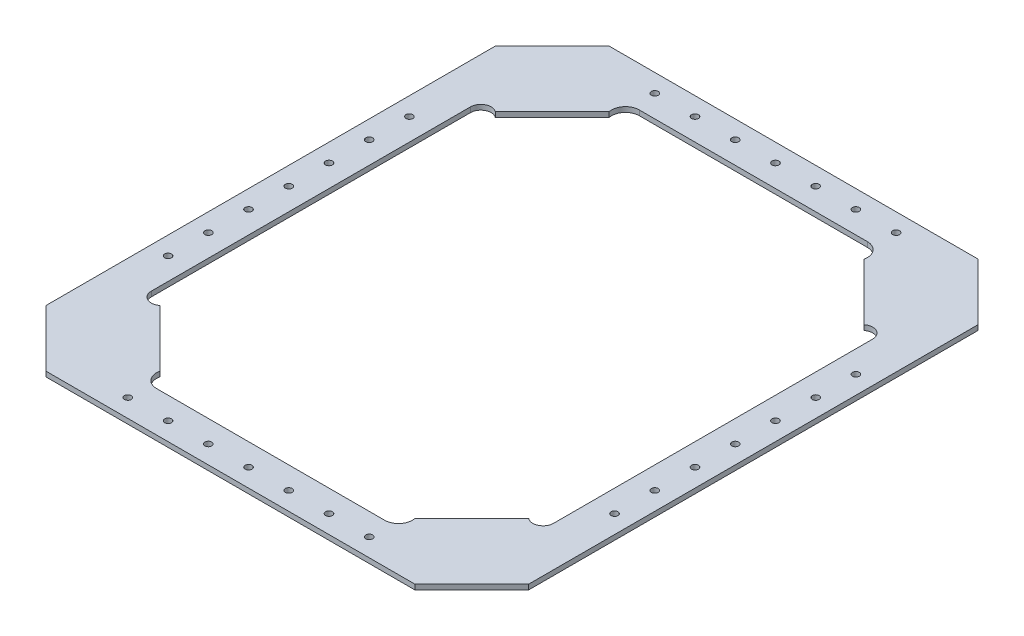
SolidWorks part; units mm, degrees
ref_plane "Front Plane" through (0, 0, 0) normal (0, 0, 1) x (1, 0, 0)
ref_plane "Top Plane" through (0, 0, 0) normal (0, 1, 0) x (1, 0, 0)
ref_plane "Right Plane" through (0, 0, 0) normal (1, 0, 0) x (0, 0, -1)
sketch "Sketch1" plane through (0, 0, 0) normal (0, 1, 0) x (1, 0, 0)
  line L0 (-152.4, 119.0596) -> (-116.479, 154.9807)
  line L1 (-116.479, 154.9807) -> (116.479, 154.9807)
  line L2 (-152.4, 119.0596) -> (-152.4, -164.6983)
  line L3 (152.4, 119.0596) -> (152.4, -164.6983)
  line L4 (152.4, 119.0596) -> (116.479, 154.9807)
  line L5 (0, 154.9807) -> (0, -200.6193) construction
  line L6 (-152.4, -22.8193) -> (152.4, -22.8193) construction
  line L7 (152.4, -164.6983) -> (116.479, -200.6193)
  line L8 (-116.479, -200.6193) -> (116.479, -200.6193)
  line L9 (-152.4, -164.6983) -> (-116.479, -200.6193)
  point P9 (0, -22.8193)
  point P11 (0, -22.8193)
  dimension "D1" = 355.6
  dimension "D3" = 50.8
  dimension "D4" = 135
extrude "Boss-Extrude1" add sketch "Sketch1" along normal blind 3.175
sketch "Sketch2" plane through (0, 3.175, 0) normal (0, 1, 0) x (1, 0, 0)
  line L0 (-152.4, -22.8193) -> (199.0625, -22.8193) construction
  line L1 (-152.4, 119.0596) -> (-152.4, -164.6983) construction
  line L2 (-91.079, 129.5807) -> (91.079, 129.5807)
  line L4 (82.443, 8.9307) -> (-74.315, 8.9307)
  line L6 (-116.479, 154.9807) -> (-91.079, 129.5807) construction
  line L7 (116.479, 154.9807) -> (91.079, 129.5807) construction
  line L8 (116.479, 154.9807) -> (-116.479, 154.9807) construction
  line L9 (-74.315, 8.9307) -> (-127, 8.9307)
  line L10 (-127, 8.9307) -> (-127, 93.6596)
  line L11 (-127, 93.6596) -> (-91.079, 129.5807)
  line L12 (82.443, 8.9307) -> (127, 8.9307)
  line L13 (127, 8.9307) -> (127, 93.6596)
  line L14 (127, 93.6596) -> (91.079, 129.5807)
  line L16 (127, -139.2983) -> (91.079, -175.2193)
  line L17 (127, -54.5693) -> (127, -139.2983)
  line L18 (82.443, -54.5693) -> (127, -54.5693)
  line L19 (-127, -139.2983) -> (-91.079, -175.2193)
  line L20 (-127, -54.5693) -> (-127, -139.2983)
  line L21 (-74.315, -54.5693) -> (-127, -54.5693)
  line L23 (82.443, -54.5693) -> (-74.315, -54.5693)
  line L25 (-91.079, -175.2193) -> (91.079, -175.2193)
  dimension "D1" = 135
  dimension "D2" = 135
  dimension "D3" = 25.4
  dimension "D4" = 90
  dimension "D5" = 90
  dimension "D6" = 50.8
  dimension "D7" = 50.8
  dimension "D8" = 31.75
  dimension "D9" = 25.4
extrude "Cut-Extrude1" cut sketch "Sketch2" against normal through all
sketch "Sketch4" plane through (0, 3.175, 0) normal (0, 1, 0) x (1, 0, 0)
  line L0 (-152.4, -22.8193) -> (171.6111, -22.8193) construction
  line L1 (-152.4, 119.0596) -> (-152.4, -164.6983) construction
  line L2 (116.479, 154.9807) -> (-116.479, 154.9807) construction
  line L4 (152.4, -164.6983) -> (152.4, 119.0596) construction
  circle A0 centre (0, 143.5507) radius 2.159
  circle A1 centre (-50.8, 143.5507) radius 2.159
  circle A2 centre (50.8, 143.5507) radius 2.159
  circle A3 centre (-25.4, 143.5507) radius 2.159
  circle A4 centre (25.4, 143.5507) radius 2.159
  circle A5 centre (-140.97, -22.8193) radius 2.159
  circle A6 centre (-140.97, 2.5807) radius 2.159
  circle A7 centre (-140.97, 27.9807) radius 2.159
  circle A8 centre (140.97, -22.8193) radius 2.159
  circle A9 centre (140.97, 2.5807) radius 2.159
  circle A10 centre (140.97, 27.9807) radius 2.159
  circle A11 centre (140.97, -73.6193) radius 2.159
  circle A12 centre (140.97, -48.2193) radius 2.159
  circle A13 centre (-140.97, -73.6193) radius 2.159
  circle A14 centre (-140.97, -48.2193) radius 2.159
  circle A15 centre (25.4, -189.1893) radius 2.159
  circle A16 centre (-25.4, -189.1893) radius 2.159
  circle A17 centre (50.8, -189.1893) radius 2.159
  circle A18 centre (-50.8, -189.1893) radius 2.159
  circle A19 centre (0, -189.1893) radius 2.159
  circle A20 centre (-76.2, 143.5507) radius 2.159
  circle A21 centre (76.2, 143.5507) radius 2.159
  circle A22 centre (-140.97, 53.3807) radius 2.159
  circle A23 centre (140.97, 53.3807) radius 2.159
  circle A24 centre (140.97, -99.0193) radius 2.159
  circle A25 centre (76.2, -189.1893) radius 2.159
  circle A26 centre (-76.2, -189.1893) radius 2.159
  circle A27 centre (-140.97, -99.0193) radius 2.159
  point P48 (0, 154.9807)
  point P56 (0, 0)
  point P57 (0, 0)
  dimension "D1" = 4.318
  dimension "D2" = 4.318
  dimension "D3" = 4.318
  dimension "D4" = 4.318
  dimension "D5" = 4.318
  dimension "D6" = 4.318
  dimension "D7" = 4.318
  dimension "D8" = 4.318
  dimension "D9" = 4.318
  dimension "D10" = 4.318
  dimension "D11" = 4.318
  dimension "D23" = 4.318
  dimension "D24" = 4.318
  dimension "D27" = 4.318
  dimension "D28" = 4.318
  dimension "D12" = 25.4
  dimension "D13" = 25.4
  dimension "D14" = 25.4
  dimension "D15" = 25.4
  dimension "D16" = 25.4
  dimension "D17" = 25.4
  dimension "D18" = 25.4
  dimension "D19" = 25.4
  dimension "D20" = 11.43
  dimension "D21" = 11.43
  dimension "D22" = 11.43
  dimension "D25" = 25.4
  dimension "D26" = 25.4
  dimension "D29" = 25.4
  dimension "D30" = 25.4
sketch "Sketch5" plane through (0, 3.175, 0) normal (0, 1, 0) x (1, 0, 0)
  line L0 (-116.479, 83.1386) -> (-80.558, 119.0596)
  line L1 (0, 129.5807) -> (0, -138.0704) construction
  line L3 (-152.4, 119.0596) -> (-152.4, 65.2582)
  line L4 (-127, 93.6596) -> (-127, 8.9307) construction
  line L5 (91.079, 129.5807) -> (-91.079, 129.5807) construction
  line L6 (-116.479, 154.9807) -> (-59.329, 154.9807)
  line L7 (116.479, 154.9807) -> (-116.479, 154.9807) construction
  line L8 (-59.329, 154.9807) -> (-59.329, 129.5807)
  line L9 (-152.4, 119.0596) -> (-116.479, 154.9807)
  line L10 (-152.4, 119.0596) -> (-152.4, -164.6983) construction
  line L12 (-152.4, 65.2582) -> (-127, 65.2582)
  line L13 (-59.329, 129.5807) -> (-72.029, 129.5807)
  line L14 (127, 65.2582) -> (127, 77.9582)
  line L15 (152.4, -22.8193) -> (-208.2375, -22.8193) construction
  line L16 (152.4, -164.6983) -> (152.4, 119.0596) construction
  line L17 (59.329, 129.5807) -> (72.029, 129.5807)
  line L18 (-127, 65.2582) -> (-127, 77.9582)
  line L19 (152.4, 65.2582) -> (127, 65.2582)
  line L20 (152.4, 119.0596) -> (116.479, 154.9807)
  line L21 (59.329, 154.9807) -> (59.329, 129.5807)
  line L22 (116.479, 154.9807) -> (59.329, 154.9807)
  line L24 (152.4, 119.0596) -> (152.4, 65.2582)
  line L25 (116.479, 83.1386) -> (80.558, 119.0596)
  line L26 (116.479, -128.7773) -> (80.558, -164.6983)
  line L27 (152.4, -164.6983) -> (152.4, -110.8969)
  line L28 (116.479, -200.6193) -> (59.329, -200.6193)
  line L29 (59.329, -200.6193) -> (59.329, -175.2193)
  line L30 (152.4, -164.6983) -> (116.479, -200.6193)
  line L31 (152.4, -110.8969) -> (127, -110.8969)
  line L32 (-127, -110.8969) -> (-127, -123.5969)
  line L33 (59.329, -175.2193) -> (72.029, -175.2193)
  line L34 (127, -110.8969) -> (127, -123.5969)
  line L35 (-59.329, -175.2193) -> (-72.029, -175.2193)
  line L36 (-152.4, -110.8969) -> (-127, -110.8969)
  line L37 (-152.4, -164.6983) -> (-116.479, -200.6193)
  line L38 (-59.329, -200.6193) -> (-59.329, -175.2193)
  line L39 (-116.479, -200.6193) -> (-59.329, -200.6193)
  line L40 (-152.4, -164.6983) -> (-152.4, -110.8969)
  line L41 (-116.479, -128.7773) -> (-80.558, -164.6983)
  arc A0 (-72.029, 129.5807) -> (-80.558, 119.0596) centre (-72.029, 120.8631) ccw
  arc A1 (-127, 77.9582) -> (-116.479, 83.1386) centre (-120.4641, 77.9582) cw
  arc A2 (127, 77.9582) -> (116.479, 83.1386) centre (120.4641, 77.9582) ccw
  arc A3 (72.029, 129.5807) -> (80.558, 119.0596) centre (72.029, 120.8631) cw
  arc A4 (72.029, -175.2193) -> (80.558, -164.6983) centre (72.029, -166.5018) ccw
  arc A5 (127, -123.5969) -> (116.479, -128.7773) centre (120.4641, -123.5969) cw
  arc A6 (-127, -123.5969) -> (-116.479, -128.7773) centre (-120.4641, -123.5969) ccw
  arc A7 (-72.029, -175.2193) -> (-80.558, -164.6983) centre (-72.029, -166.5018) cw
  dimension "D3" = 12.7
  dimension "D1" = 50.8
  dimension "D2" = 50.8
  dimension "D4" = 12.7
  dimension "D5" = 57.15
  dimension "D6" = 53.8014
extrude "Boss-Extrude2" add sketch "Sketch5" against normal blind 3.175
extrude "Cut-Extrude2" cut sketch "Sketch4" against normal through all
sketch "Sketch6" plane through (0, 3.175, 0) normal (0, 1, 0) x (1, 0, 0)
  line L0 (-127, 77.9582) -> (-127, 8.9307) construction
  line L1 (-127, 27.2649) -> (127, 27.2649)
  line L2 (-127, 27.2649) -> (-127, -79.6155)
  line L3 (-127, -79.6155) -> (127, -79.6155)
  line L4 (127, 27.2649) -> (127, -79.6155)
  line L5 (127, 8.9307) -> (127, 77.9582) construction
  point P4 (-215.939, 3.0616)
extrude "Cut-Extrude3" cut sketch "Sketch6" against normal through all
